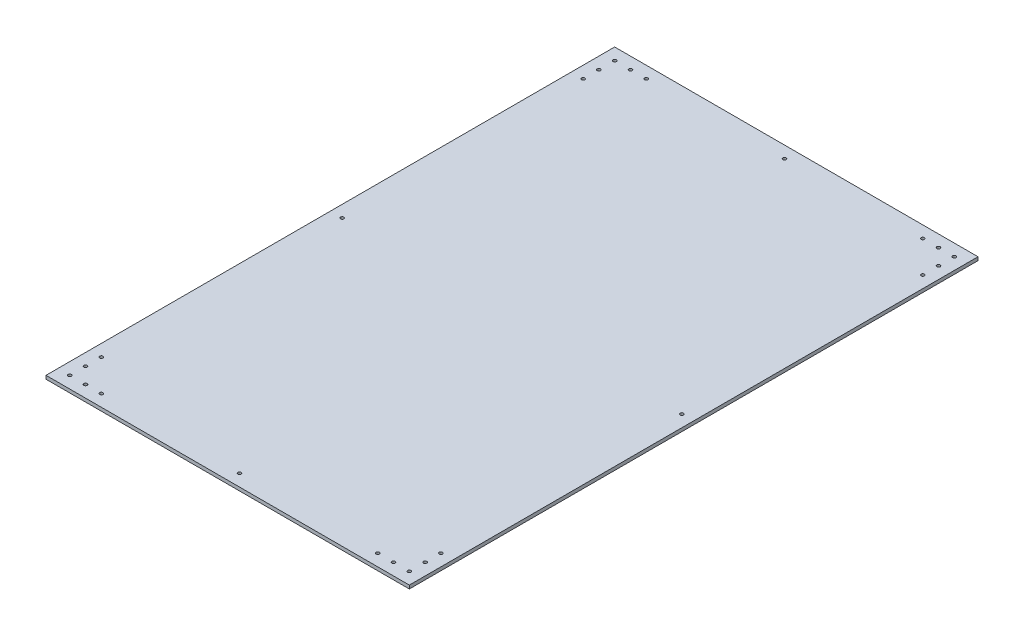
SolidWorks part; units mm, degrees
ref_plane "Front Plane" through (0, 0, 0) normal (0, 0, 1) x (1, 0, 0)
ref_plane "Top Plane" through (0, 0, 0) normal (0, 1, 0) x (1, 0, 0)
ref_plane "Right Plane" through (0, 0, 0) normal (1, 0, 0) x (0, 0, -1)
sketch "Sketch1" plane through (0, 0, 0) normal (0, 1, 0) x (1, 0, 0)
  line L1 (-304.8, 609.6) -> (304.8, 609.6)
  line L2 (-304.8, 609.6) -> (-304.8, -609.6)
  line L3 (-304.8, -609.6) -> (304.8, -609.6)
  line L4 (304.8, 609.6) -> (304.8, -609.6)
  line L5 (-304.8, 609.6) -> (304.8, -609.6) construction
  line L6 (-304.8, -609.6) -> (304.8, 609.6) construction
  point P0 (0, 0)
  dimension "D1" = 609.6
  dimension "D2" = 1219.2
extrude "Boss-Extrude1" add sketch "Sketch1" along normal blind 5.5
sketch "Sketch2" plane through (0, 5.5, 0) normal (0, 1, 0) x (1, 0, 0)
  line L0 (-279.4, 609.6) -> (-279.4, -609.6)
  line L1 (304.8, 609.6) -> (-304.8, 609.6) construction
  line L2 (-304.8, -609.6) -> (304.8, -609.6) construction
  line L3 (304.8, -609.6) -> (304.8, 609.6) construction
  line L4 (-279.4, 307.34) -> (304.8, 307.34)
  dimension "D1" = 1219.2
  dimension "D2" = 584.2
  dimension "D3" = 302.26
extrude "Extrude-Thin1" add sketch "Sketch2" along normal blind 25.4 thin contours L4 thin type one direction wall 2.54
extrude "Extrude-Thin2" add sketch "Sketch2<3>" along normal blind 25.4 thin thin type one direction wall 2.54
sketch "Sketch2<3>" plane through (0, 5.5, 0) normal (0, 1, 0) x (1, 0, 0) same geometry as "Sketch2"
sketch "Sketch3" plane through (0, 5.5, 0) normal (0, 1, 0) x (1, 0, 0)
  line L0 (-279.4, -590.55) -> (304.8, -590.55) construction
  line L1 (-279.4, 304.8) -> (-279.4, -609.6) construction
  line L2 (304.8, -609.6) -> (304.8, 304.8) construction
  line L3 (-279.4, -609.6) -> (304.8, -609.6) construction
  line L4 (-260.35, -609.6) -> (-260.35, 304.8) construction
  line L5 (-279.4, 304.8) -> (304.8, 304.8) construction
  line L6 (-279.4, 304.8) -> (-279.4, -609.6) construction
  line L7 (-279.4, 285.75) -> (304.8, 285.75) construction
  line L8 (285.75, -609.6) -> (285.75, 304.8) construction
  line L9 (-279.4, 304.8) -> (304.8, 304.8) construction
  line L10 (-260.35, -152.4) -> (285.75, -152.4) construction
  line L11 (12.7, 285.75) -> (12.7, -590.55) construction
  point P20 (-260.35, 285.75)
  point P21 (-260.35, 260.35)
  point P22 (-234.95, 285.75)
  point P23 (-260.35, 234.95)
  point P24 (-209.55, 285.75)
  point P29 (285.75, 234.95)
  point P30 (12.7, 285.75)
  point P31 (-260.35, -152.4)
  point P32 (12.7, -590.55)
  point P33 (285.75, -152.4)
  point P34 (285.75, 260.35)
  point P35 (285.75, 285.75)
  point P36 (260.35, 285.75)
  point P37 (234.95, 285.75)
  point P38 (285.75, -539.75)
  point P39 (285.75, -565.15)
  point P40 (285.75, -590.55)
  point P41 (260.35, -590.55)
  point P42 (234.95, -590.55)
  point P43 (-209.55, -590.55)
  point P44 (-234.95, -590.55)
  point P45 (-260.35, -590.55)
  point P46 (-260.35, -565.15)
  point P47 (-260.35, -539.75)
  dimension "D1" = 19.05
  dimension "D2" = 19.05
  dimension "D3" = 19.05
  dimension "D4" = 19.05
  dimension "D5" = 0
  dimension "D6" = 25.4
  dimension "D7" = 25.4
  dimension "D8" = 25.4
  dimension "D9" = 25.4
hole_wizard "Ø5.3 (5.3) Diameter Hole1" positions "Sketch4" profile "Sketch5" hole size "Ø5.3" standard "ANSI Metric" end condition through all
sketch "Sketch4" plane through (0, 5.5, 0) normal (0, 1, 0) x (1, 0, 0)
  point P0 (-260.35, 285.75)
  point P3 (-234.95, 285.75)
  point P6 (-209.55, 285.75)
  point P9 (-260.35, 260.35)
  point P12 (-260.35, 234.95)
  point P15 (12.7, 285.75)
  point P18 (234.95, 285.75)
  point P21 (260.35, 285.75)
  point P24 (285.75, 285.75)
  point P27 (285.75, 260.35)
  point P30 (285.75, 234.95)
  point P33 (-260.35, -152.4)
  point P36 (285.75, -152.4)
  point P39 (-260.35, -539.75)
  point P42 (-260.35, -565.15)
  point P45 (-260.35, -590.55)
  point P48 (-234.95, -590.55)
  point P51 (-209.55, -590.55)
  point P54 (12.7, -590.55)
  point P57 (234.95, -590.55)
  point P60 (260.35, -590.55)
  point P63 (285.75, -590.55)
  point P66 (285.75, -565.15)
  point P69 (285.75, -539.75)
sketch "Sketch5" plane through (-260.35, 5.5, -285.75) normal (1, 0, 0) x (0, 0, 1)
  line L0 (0, 0) -> (0, 5.5)
  line L1 (0, 5.5) -> (2.65, 5.5)
  line L2 (2.65, 5.5) -> (2.65, 0)
  line L5 (2.65, 0) -> (0, 0)
  line L11 (0, -6.35) -> (0, 107.95) construction
  dimension "Thru Hole Dia." = 5.3
  dimension "Thru Hole Depth" = 5.5
sketch "Sketch6" plane through (0, 0, 0) normal (0, -1, 0) x (1, 0, 0)
  line L0 (304.8, -609.6) -> (-304.8, -609.6) construction
  line L1 (-304.8, 609.6) -> (-279.4, 609.6)
  line L2 (-304.8, 609.6) -> (-304.8, -609.6)
  line L3 (-304.8, -609.6) -> (-279.4, -609.6)
  line L4 (-279.4, 609.6) -> (-279.4, -304.8)
  line L5 (304.8, 609.6) -> (304.8, -609.6) construction
  line L6 (-279.4, -609.6) -> (304.8, -609.6)
  line L8 (-279.4, -304.8) -> (304.8, -304.8)
  line L9 (304.8, -609.6) -> (304.8, -304.8)
  dimension "D1" = 25.4
  dimension "D2" = 304.8
  dimension "D3" = 25.4
extrude "Cut-Extrude1" cut sketch "Sketch6" against normal up to next
